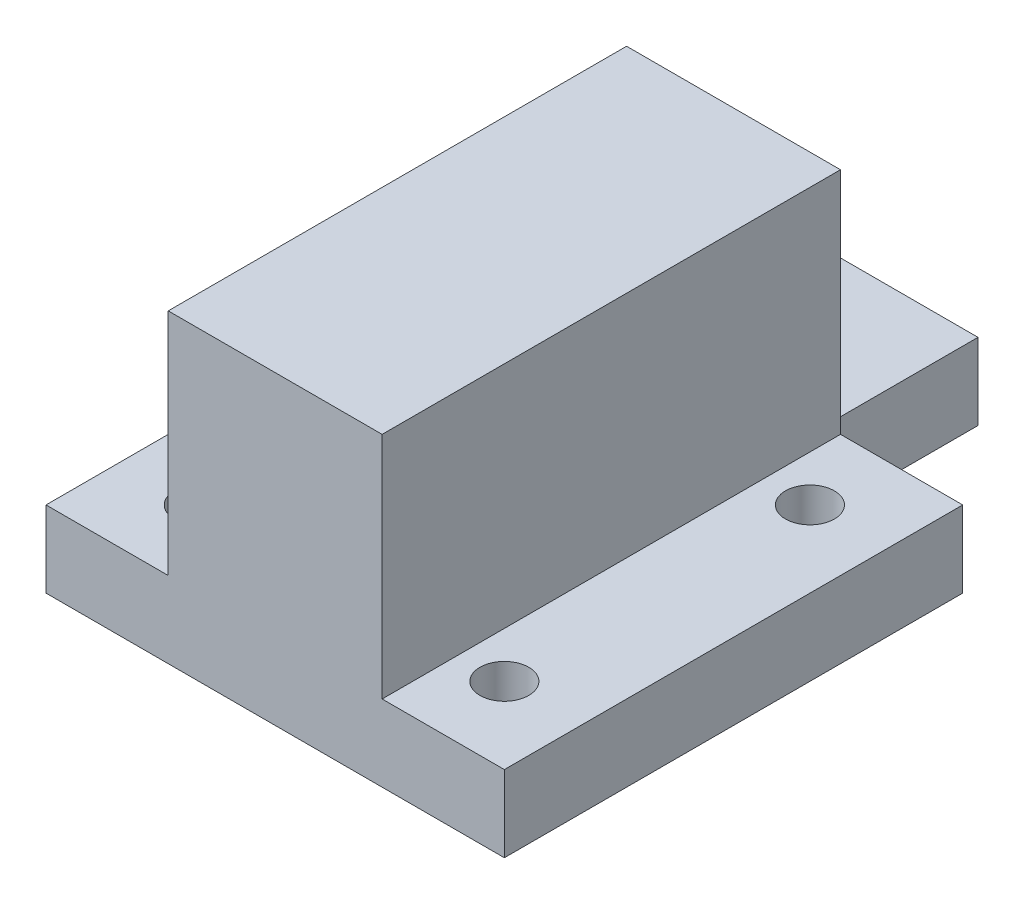
SolidWorks part; units mm, degrees
ref_plane "Front Plane" through (0, 0, 0) normal (0, 0, 1) x (1, 0, 0)
ref_plane "Top Plane" through (0, 0, 0) normal (0, 1, 0) x (1, 0, 0)
ref_plane "Right Plane" through (0, 0, 0) normal (1, 0, 0) x (0, 0, -1)
sketch "Sketch1" plane through (0, 0, 0) normal (0, 1, 0) x (1, 0, 0)
  line L1 (-15, 15) -> (15, 15)
  line L2 (-15, 15) -> (-15, -15)
  line L3 (-15, -15) -> (15, -15)
  line L4 (15, 15) -> (15, -15)
  line L5 (-15, 15) -> (15, -15) construction
  line L6 (-15, -15) -> (15, 15) construction
  line L7 (-6, 15) -> (6, 15)
  line L8 (-6, 15) -> (-6, 25)
  line L9 (-6, 25) -> (6, 25)
  line L10 (6, 15) -> (6, 25)
  circle A0 centre (-10, 10) radius 1.6
  circle A1 centre (10, 10) radius 1.6
  circle A2 centre (10, -10) radius 1.6
  circle A3 centre (-10, -10) radius 1.6
  point P0 (0, 0)
  dimension "D3" = 5
  dimension "D4" = 5
  dimension "D5" = 3.2
  dimension "D1" = 30
  dimension "D2" = 30
  dimension "D8" = 6
  dimension "D9" = 6
  dimension "D10" = 10
  dimension "D6" = 2
  dimension "D7" = 2
extrude "Boss-Extrude3" add sketch "Sketch1" along normal blind 5 contours L4 L1 L2 L3 A3 A2 A1 A0 | L1 L10 L9 L8 region at (0, 0, 0) region at (0, 0, -20)
sketch "Sketch2" plane through (0, 5, 0) normal (0, 1, 0) x (1, 0, 0)
  line L0 (15, 15) -> (-15, 15) construction
  line L1 (-7, 15) -> (7, 15)
  line L2 (-7, 15) -> (-7, -15)
  line L3 (-7, -15) -> (7, -15)
  line L4 (7, 15) -> (7, -15)
  line L5 (-15, -15) -> (15, -15) construction
  circle A0 centre (10, -10) radius 1.6 construction
  circle A1 centre (-10, -10) radius 1.6 construction
  dimension "D1" = 3
  dimension "D2" = 3
extrude "Boss-Extrude2" add sketch "Sketch2" along normal blind 15
